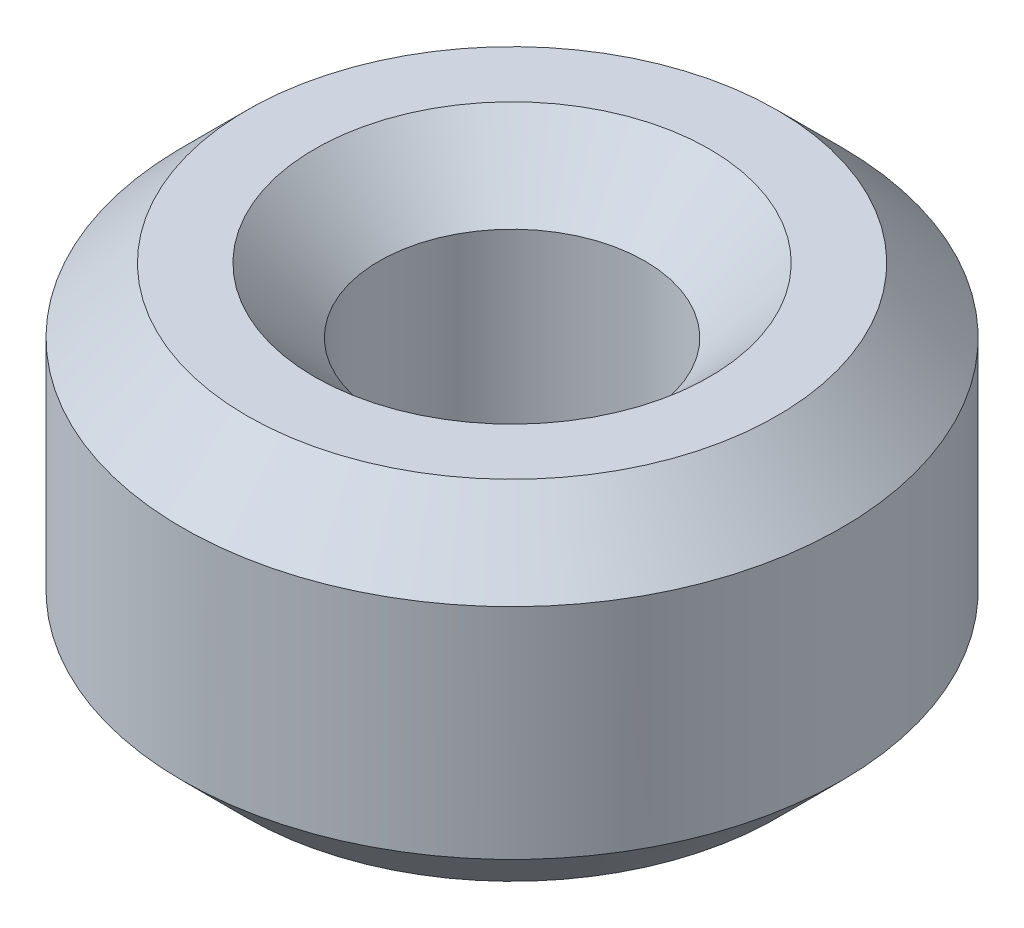
SolidWorks part; units mm, degrees
ref_plane "Front Plane" through (0, 0, 0) normal (0, 0, 1) x (1, 0, 0)
ref_plane "Top Plane" through (0, 0, 0) normal (0, 1, 0) x (1, 0, 0)
ref_plane "Right Plane" through (0, 0, 0) normal (1, 0, 0) x (0, 0, -1)
sketch "Sketch1" plane through (0, 0, 0) normal (0, 1, 0) x (1, 0, 0)
  circle A0 centre (0, 0) radius 17.5
  dimension "SLEEVE_OD" = 35
extrude "Boss-Extrude1" add sketch "Sketch1" along normal blind 18.4887
sketch "Sketch2" plane through (0, 0, 0) normal (0, 1, 0) x (1, 0, 0)
  circle A0 centre (0, 0) radius 7.0502
  dimension "BORE_D" = 14.1004
extrude "Cut-Extrude1" cut sketch "Sketch2" along normal through all
chamfer "Chamfer1" distance 3.4318 angle 45 4 edges at (0, 18.4887, 7.0502) (0, 0, 7.0502) (0, 0, 17.5) (0, 18.4887, 17.5)
